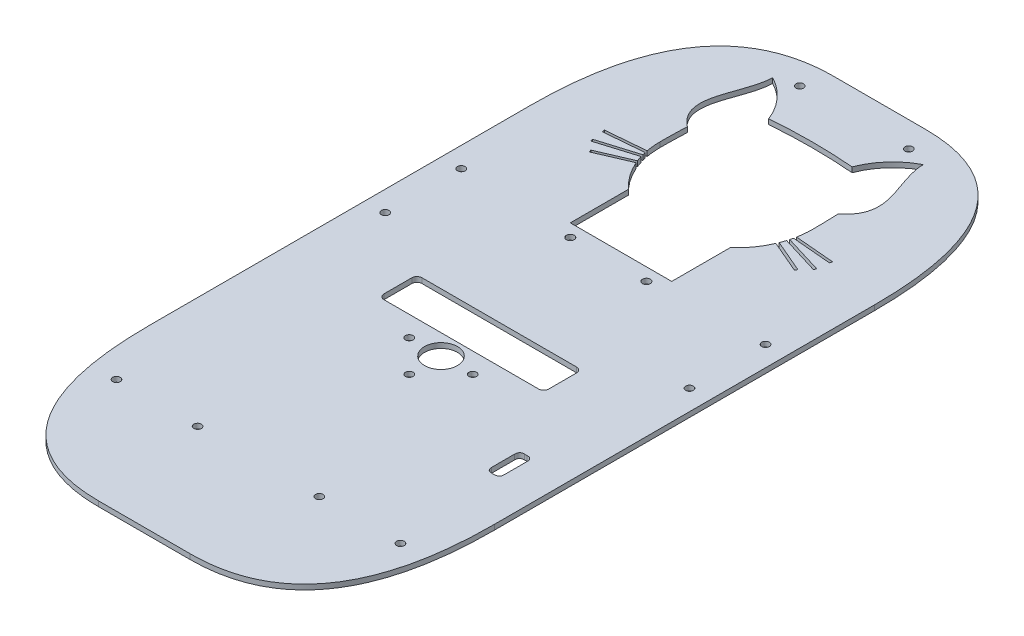
SolidWorks part; units mm, degrees
ref_plane "Спереди" through (0, 0, 0) normal (0, 0, 1) x (1, 0, 0)
ref_plane "Сверху" through (0, 0, 0) normal (0, 1, 0) x (1, 0, 0)
ref_plane "Справа" through (0, 0, 0) normal (1, 0, 0) x (0, 0, -1)
sketch "Эскиз1" plane through (0, 0, 0) normal (0, 1, 0) x (1, 0, 0)
  line L0 (0, 160) -> (0, -130) construction
  line L1 (-68, 160) -> (68, 160)
  line L2 (-68, 160) -> (-68, -130)
  line L3 (-68, -130) -> (68, -130)
  line L4 (68, 160) -> (68, -130)
  line L5 (-68, 0) -> (68, 0) construction
  dimension "D1" = 136
  dimension "D2" = 160
  dimension "D3" = 130
extrude "тело" add sketch "Эскиз1" along normal blind 2
sketch "Эскиз12" plane through (0, 2, 0) normal (0, 1, 0) x (1, 0, 0)
  line L0 (0, 160) -> (0, -130) construction
  line L1 (68, 160) -> (-68, 160) construction
  line L2 (-68, -130) -> (68, -130) construction
  line L3 (60, 55) -> (60, 25) construction
  line L4 (60, 40) -> (-60, 40) construction
  line L5 (-60, 55) -> (-60, 25) construction
  circle A0 centre (60, 55) radius 1.5
  circle A1 centre (-60, 55) radius 1.5
  circle A2 centre (-60, 25) radius 1.5
  circle A3 centre (60, 25) radius 1.5
  point P12 (-60, 40)
  point P17 (0, 40)
  dimension "D2" = 3
  dimension "D1" = 30
  dimension "D3" = 60
  dimension "D4" = 40
extrude "крепление подвески" cut sketch "Эскиз12" against normal through all
sketch "Эскиз8" plane through (0, 2, 0) normal (0, 1, 0) x (1, 0, 0)
  line L0 (-20, -130) -> (20, -130) construction
  line L1 (0, -130) -> (0, 160) construction
  line L2 (-68, -130) -> (68, -130) construction
  line L3 (68, 160) -> (-68, 160) construction
  circle A0 centre (-20, -130) radius 1.5
  circle A1 centre (20, -130) radius 1.5
  point P10 (0, -130)
  dimension "D1" = 3
  dimension "D2" = 40
  dimension "D3" = 130
extrude "крепление камеры" [suppressed] cut sketch "Эскиз8" against normal through all and the other way through all
sketch "Эскиз13" plane through (0, 2, 0) normal (0, 1, 0) x (1, 0, 0)
  line L0 (0, 160) -> (0, -130) construction
  line L1 (68, 160) -> (-68, 160) construction
  line L2 (-68, -130) -> (68, -130) construction
  line L3 (-57, 125) -> (57, 125) construction
  line L4 (-68, 15) -> (68, 15) construction
  line L5 (-57, -10) -> (57, -10) construction
  line L6 (-68, 160) -> (-68, -130) construction
  line L7 (-57, -85) -> (57, -85) construction
  line L8 (68, -130) -> (68, 160) construction
  line L9 (-25, 125) -> (-57, 125) construction
  line L10 (25, 125) -> (57, 125) construction
  line L11 (-57, -10) -> (-25, -10) construction
  line L12 (25, -10) -> (57, -10) construction
  line L13 (-57, -85) -> (-25, -85) construction
  line L14 (25, -85) -> (57, -85) construction
  circle A0 centre (-57, 125) radius 1.5
  circle A1 centre (57, 125) radius 1.5
  circle A2 centre (57, -10) radius 1.5
  circle A3 centre (-57, -10) radius 1.5
  circle A4 centre (-57, -85) radius 1.5
  circle A5 centre (57, -85) radius 1.5
  circle A6 centre (-25, 125) radius 1.5
  circle A7 centre (25, 125) radius 1.5
  circle A8 centre (25, -10) radius 1.5
  circle A9 centre (-25, -10) radius 1.5
  circle A10 centre (-25, -85) radius 1.5
  circle A11 centre (25, -85) radius 1.5
  point P18 (0, 125)
  point P19 (0, -10)
  point P20 (0, -85)
  point P27 (0, 15)
  dimension "D1" = 3
  dimension "D2" = 110
  dimension "D3" = 25
  dimension "D4" = 100
  dimension "D5" = 114
  dimension "D6" = 32
  dimension "D7" = 32
  dimension "D8" = 32
  dimension "D9" = 32
  dimension "D10" = 32
  dimension "D11" = 32
extrude "крепления уголков" [suppressed] cut sketch "Эскиз13" against normal through all
sketch "Эскиз9" plane through (0, 2, 0) normal (0, 1, 0) x (1, 0, 0)
  line L0 (0, -50) -> (0, 50) construction
  line L2 (-68, -130) -> (68, -130) construction
  circle A0 centre (0, -13) radius 6.5
  circle A1 centre (0, -13) radius 12.5 construction
  circle A2 centre (0, -0.5) radius 1.5
  circle A3 centre (12.5, -13) radius 1.5
  circle A4 centre (-12.5, -13) radius 1.5
  circle A5 centre (0, -25.5) radius 1.5
  dimension "D2" = 13
  dimension "D3" = 25
  dimension "D4" = 3
  dimension "D1" = 117
extrude "ось вращения качалки" cut sketch "Эскиз9" against normal through all
sketch "Эскиз5" plane through (0, 2, 0) normal (0, 1, 0) x (1, 0, 0)
  line L0 (-50, -65) -> (50, -25) construction
  line L1 (-50, -25) -> (50, -25) construction
  line L2 (-50, -25) -> (-50, -65) construction
  line L3 (-50, -65) -> (50, -65) construction
  line L4 (50, -25) -> (50, -65) construction
  line L5 (-50, -25) -> (50, -65) construction
  line L6 (-68, -130) -> (68, -130) construction
  circle A0 centre (-50, -25) radius 1.5
  circle A1 centre (50, -25) radius 1.5
  circle A2 centre (50, -65) radius 1.5
  circle A3 centre (-50, -65) radius 1.5
  point P12 (0, -45)
  dimension "D1" = 3
  dimension "D2" = 100
  dimension "D3" = 40
  dimension "D4" = 65
extrude "крепление raspberry" [suppressed] cut sketch "Эскиз5" against normal through all
sketch "Эскиз11" plane through (0, 2, 0) normal (0, 1, 0) x (1, 0, 0)
  line L0 (-32.5, 2.5) -> (32.5, 2.5) construction
  line L1 (-32.5, 10) -> (32.5, 10)
  line L2 (-32.5, 10) -> (-32.5, -5)
  line L3 (-32.5, -5) -> (32.5, -5)
  line L4 (32.5, 10) -> (32.5, -5)
  point P11 (0, 10)
  dimension "D1" = 65
  dimension "D2" = 15
extrude "отверстие под провода на нижний этаж" cut sketch "Эскиз11" against normal through all
fillet "Скругление3" radius 2 4 edges at (-32.5, 1, 5) (32.5, 1, 5) (32.5, 1, -10) (-32.5, 1, -10)
sketch "Эскиз14" [suppressed] plane through (0, 2, 0) normal (0, 1, 0) x (1, 0, 0)
  line L0 (0, 160) -> (0, -130) construction
  line L1 (68, 160) -> (-68, 160) construction
  line L2 (-68, -130) -> (68, -130) construction
  line L3 (-47.5, -125) -> (47.5, -125) construction
  line L4 (47.5, -115) -> (47.5, -135) construction
  line L5 (-12.5, -95) -> (12.5, -95) construction
  line L6 (-47.5, -115) -> (-47.5, -135) construction
  circle A0 centre (-47.5, -115) radius 1.5
  circle A1 centre (-47.5, -135) radius 1.5
  circle A2 centre (47.5, -115) radius 1.5
  circle A3 centre (47.5, -135) radius 1.5
  point P8 (0, -125)
  point P14 (-47.5, -125)
  point P15 (47.5, -125)
  dimension "D1" = 3
  dimension "D2" = 20
  dimension "D3" = 30
  dimension "D4" = 95
extrude "крепление стопоров" [suppressed] cut sketch "Эскиз14" against normal through all
sketch "Эскиз15" plane through (0, 2, 0) normal (0, 1, 0) x (1, 0, 0)
  line L0 (-21.5, 150) -> (21.5, 150) construction
  line L1 (68, 160) -> (-68, 160) construction
  circle A0 centre (21.5, 150) radius 1.5
  circle A1 centre (-21.5, 150) radius 1.5
  point P6 (0, 150)
  dimension "D1" = 3
  dimension "D2" = 10
  dimension "D3" = 43
extrude "Крепление фронтальной камеры" cut sketch "Эскиз15" against normal up to next
sketch "Эскиз16" plane through (0, 2, 0) normal (0, 1, 0) x (1, 0, 0)
  line L0 (-56, -85) -> (-24, -85) construction
  line L1 (-68, -130) -> (68, -130) construction
  line L2 (-68, 160) -> (-68, -130) construction
  line L3 (0, -130) -> (0, 160) construction
  line L4 (68, 160) -> (-68, 160) construction
  circle A0 centre (-56, -85) radius 1.5
  circle A1 centre (-24, -85) radius 1.5
  circle A2 centre (24, -85) radius 1.5
  circle A3 centre (56, -85) radius 1.5
  dimension "D1" = 32
  dimension "D4" = 3
  dimension "D2" = 45
  dimension "D3" = 12
extrude "Крепление силовых уголков со стороны буллета" cut sketch "Эскиз16" against normal up to next
sketch "Эскиз17" plane through (0, 2, 0) normal (0, 1, 0) x (1, 0, 0)
  line L1 (48, -30) -> (53, -30)
  line L2 (48, -30) -> (48, -43)
  line L3 (48, -43) -> (53, -43)
  line L4 (53, -30) -> (53, -43)
  dimension "D2" = 13
  dimension "D3" = 5
extrude "Отверстие по дпитание сервоприводов и шилда" cut sketch "Эскиз17" against normal up to next
sketch "Эскиз18" plane through (0, 2, 0) normal (0, 1, 0) x (1, 0, 0)
  line L0 (0, 0) -> (0, 160) construction
  line L1 (68, 160) -> (-68, 160) construction
  line L2 (-20, 58) -> (20, 58)
  line L3 (20, 58) -> (20, 81)
  line L5 (-20, 81) -> (-20, 58)
  line L6 (10, 58) -> (10, 43)
  line L7 (10, 43) -> (-10, 43)
  line L8 (-10, 43) -> (-10, 58)
  line L9 (28.2843, 93.3607) -> (-28.2843, 93.3607)
  line L11 (-29.2696, 96.7813) -> (-44.8695, 95.4286)
  line L12 (15, 53) -> (-15, 53) construction
  line L13 (-28.6963, 94.613) -> (-43.9353, 89.9676)
  line L16 (-27.5654, 91.5223) -> (-40.4203, 86.0016)
  line L17 (-29.474, 97.7673) -> (-44.9559, 96.4249)
  line L18 (-28.972, 95.5744) -> (-44.2269, 90.9242)
  line L19 (-27.9447, 92.4477) -> (-40.8149, 86.9204)
  line L20 (-44.9559, 96.4249) -> (-44.8695, 95.4286)
  line L21 (-44.2269, 90.9242) -> (-43.9353, 89.9676)
  line L22 (-40.8149, 86.9204) -> (-40.4203, 86.0016)
  line L23 (-29.356, 97.7776) -> (-44.9559, 96.4249) construction
  line L24 (-28.6804, 94.6179) -> (-43.9353, 89.9676) construction
  line L25 (-27.5501, 91.5289) -> (-40.4203, 86.0016) construction
  line L26 (40.8149, 86.9204) -> (40.4203, 86.0016)
  line L27 (44.2269, 90.9242) -> (43.9353, 89.9676)
  line L28 (44.9559, 96.4249) -> (44.8695, 95.4286)
  line L29 (27.9447, 92.4477) -> (40.8149, 86.9204)
  line L30 (28.972, 95.5744) -> (44.2269, 90.9242)
  line L31 (29.474, 97.7673) -> (44.9559, 96.4249)
  line L32 (27.5654, 91.5223) -> (40.4203, 86.0016)
  line L33 (28.6963, 94.613) -> (43.9353, 89.9676)
  line L34 (29.2696, 96.7813) -> (44.8695, 95.4286)
  arc A0 (20, 81) -> (-20, 81) centre (0, 103.3607) ccw construction
  circle A1 centre (15, 53) radius 1.55
  circle A2 centre (-15, 53) radius 1.55
  arc A4 (-30, 103.3607) -> (-28.2843, 131.3607) centre (199.3322, 103.3607) cw
  arc A5 (-28.2843, 131.3607) -> (28.2843, 131.3607) centre (0, -67.6393) cw
  arc A6 (28.2843, 131.3607) -> (30, 103.3607) centre (-199.3322, 103.3607) cw
  arc A7 (-20, 81) -> (-27.5654, 91.5223) centre (0, 103.3607) cw
  arc A8 (20, 81) -> (27.5654, 91.5223) centre (0, 103.3607) ccw
  arc A9 (29.474, 97.7673) -> (30, 103.3607) centre (0, 103.3607) ccw
  arc A10 (-29.7135, 147.5209) -> (-16.4423, 132.687) centre (-42.569, 122.6661) cw
  arc A11 (29.7135, 147.5209) -> (16.4423, 132.687) centre (42.569, 122.6661) ccw
  arc A12 (28.972, 95.5744) -> (29.2696, 96.7813) centre (0, 103.3607) ccw
  arc A13 (27.9447, 92.4477) -> (28.6963, 94.613) centre (0, 103.3607) ccw
  arc A14 (-27.9447, 92.4477) -> (-28.6963, 94.613) centre (0, 103.3607) cw
  arc A15 (-28.972, 95.5744) -> (-29.2696, 96.7813) centre (0, 103.3607) cw
  arc A16 (-29.474, 97.7673) -> (-30, 103.3607) centre (0, 103.3607) cw
  spline S0 degree 3 poles (-29.7571, 113.9123) (-42.1018, 123.5014) (-29.7562, 136.265) (-29.7135, 147.5209) knots 0 0 0 0 1 1 1 1
  spline S1 degree 3 poles (29.7571, 113.9123) (42.1018, 123.5014) (29.7562, 136.265) (29.7135, 147.5209) knots 0 0 0 0 1 1 1 1
  point P9 (0, 43)
  point P15 (0, 58)
  point P25 (0, 53)
  dimension "D6" = 60
  dimension "D8" = 3.1
  dimension "D1" = 40
  dimension "D2" = 20
  dimension "D3" = 15
  dimension "D4" = 23
  dimension "D5" = 10
  dimension "D9" = 5
  dimension "D10" = 30
  dimension "D11" = 38
  dimension "D12" = 56.5685
  dimension "D13" = 1
  dimension "D14" = 1
  dimension "D15" = 1
fillet "Скругление4" radius 50 2 edges at (68, 1, 130) (-68, 1, -160) second distance 70 conic rho 0.5 first distance on face at (0, 1, 130) first distance on face at (0, 1, -160)
fillet "Скругление5" radius 70 2 edges at (-68, 1, 130) (68, 1, -160) second distance 50 conic rho 0.5 first distance on face at (-68, 1.25, -35) first distance on face at (68, 1.25, 5)
fillet "Скругление6" radius 2 4 edges at (48, 1, 43) (53, 1, 43) (48, 1, 30) (53, 1, 30) conic rho 0.5
sketch "Эскиз19" plane through (0, 2, 0) normal (0, 1, 0) x (1, 0, 0)
  line L1 (-95.3857, 162.9355) -> (76.7354, 162.9355)
  line L2 (-95.3857, 162.9355) -> (-95.3857, 60)
  line L3 (-95.3857, 60) -> (76.7354, 60)
  line L4 (76.7354, 162.9355) -> (76.7354, 60)
  circle A0 centre (-60, 55) radius 1.5 construction
  dimension "D1" = 5
extrude "Вырез-Вытянуть3" [suppressed] cut sketch "Эскиз19" against normal up to next
fillet "Скругление8" [suppressed] radius 10
extrude "Вырез под манипулятор" cut sketch "Эскиз18" against normal up to next contours S0 A4 A5 A10 | A6 S1 A11 A5 | A16 L17 L20 L11 A15 L18 L21 L13 A14 L9 A13 L33 L27 L30 A12 L34 L28 L31 A9 A6 A5 A4 | A14 L19 L22 L16 A7 L5 L2 L3 A8 L32 L26 L29 A13 L9 | A1 | A2 region at (0, 2, -76.9456) region at (0, 2, -112.4371) region at (-27.968, 2, -132.7806) region at (27.968, 2, -132.7806) region at (15, 2, -53) region at (-15, 2, -53)
